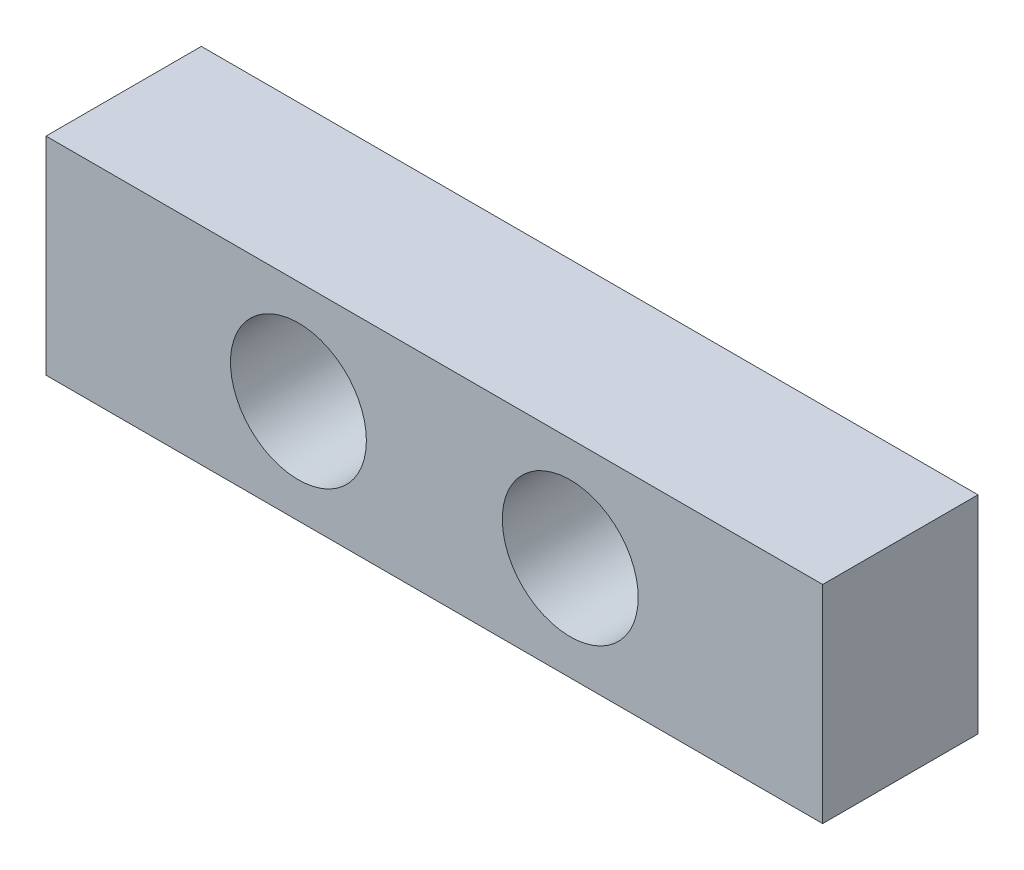
SolidWorks part; units mm, degrees
ref_plane "xy_plane" through (0, 0, 0) normal (0, 0, 1) x (1, 0, 0)
ref_plane "zx_plane" through (0, 0, 0) normal (0, 1, 0) x (1, 0, 0)
ref_plane "yz_plane" through (0, 0, 0) normal (1, 0, 0) x (0, 0, -1)
ref_axis "x_axis" through (-80.9, 0, 0) along (1, 0, 0)
ref_axis "y_axis" through (0, -50, 0) along (0, 1, 0)
ref_axis "z_axis" through (0, 0, -80.9) along (0, 0, 1)
ref_plane "xMid_plane" through (0, 0, 0) normal (1, 0, 0) x (0, 0, -1)
ref_plane "xMin_plane" through (-15, 0, 0) normal (1, 0, 0) x (0, 0, -1)
ref_plane "xMax_plane" through (15, 0, 0) normal (1, 0, 0) x (0, 0, -1)
ref_plane "yMid_plane" through (0, 0, 0) normal (0, 1, 0) x (1, 0, 0)
ref_plane "yMin_plane" through (0, -4, 0) normal (0, 1, 0) x (1, 0, 0)
ref_plane "yMax_plane" through (0, 4, 0) normal (0, 1, 0) x (1, 0, 0)
ref_plane "zMid_plane" through (0, 0, 0) normal (0, 0, 1) x (1, 0, 0)
ref_plane "zMin_plane" through (0, 0, -3) normal (0, 0, 1) x (1, 0, 0)
ref_plane "zMax_plane" through (0, 0, 3) normal (0, 0, 1) x (1, 0, 0)
sketch "projectionXy_sketch" plane through (0, 0, 0) normal (0, 0, 1) x (1, 0, 0)
  line L0 (55, 4) -> (-55, 4) construction
  line L1 (-15, 4) -> (15, 4)
  line L2 (-15, 4) -> (-15, -4)
  line L3 (-15, -4) -> (15, -4)
  line L4 (15, 4) -> (15, -4)
  line L5 (55, -4) -> (-55, -4) construction
  line L6 (15, -55) -> (15, 55) construction
  line L7 (-15, -55) -> (-15, 55) construction
extrude "mainBody_extrude" add sketch "projectionXy_sketch" along normal up to surface (3 mm away) from surface up to plane "zMax_plane" starting at plane "zMin_plane"
sketch "viseScrewClearanceHoles_sketch" plane through (0, 0, 0) normal (0, 0, 1) x (1, 0, 0)
  line L0 (-5.25, 0) -> (5.25, 0) construction
  line L1 (0, -55) -> (0, 55) construction
  line L3 (55, 0) -> (-55, 0) construction
  circle A0 centre (-5.25, 0) radius 2.625
  circle A1 centre (5.25, 0) radius 2.625
  point P0 (0, 0)
  point P2 (0, 0)
  point P6 (0, 0)
  point P11 (19.8039, 0)
  dimension "D1" = 5.25
  dimension "D2" = 10.5
extrude "viseScrewClearanceHoles_cut" cut sketch "viseScrewClearanceHoles_sketch" against normal through all both and the other way through all from surface starting at plane "zMid_plane"
equation "\"D1@xMin_plane\" = \"externalParameters.this.extent.x\" / 2"
equation "\"D1@xMax_plane\" = \"externalParameters.this.extent.x\" / 2"
equation "\"D1@yMin_plane\" = \"externalParameters.this.extent.y\" / 2"
equation "\"D1@yMax_plane\" = \"externalParameters.this.extent.y\" / 2"
equation "\"D1@zMin_plane\"= \"externalParameters.this.extent.z\" / 2"
equation "\"D1@zMax_plane\" = \"externalParameters.this.extent.z\" / 2"
equation "\"D1@viseScrewClearanceHoles_sketch\" = \"externalParameters.arm.viseScrew.closeFitDiameter\""
equation "\"D2@viseScrewClearanceHoles_sketch\" = \"externalParameters.arm.viseScrews.intervalX\""
